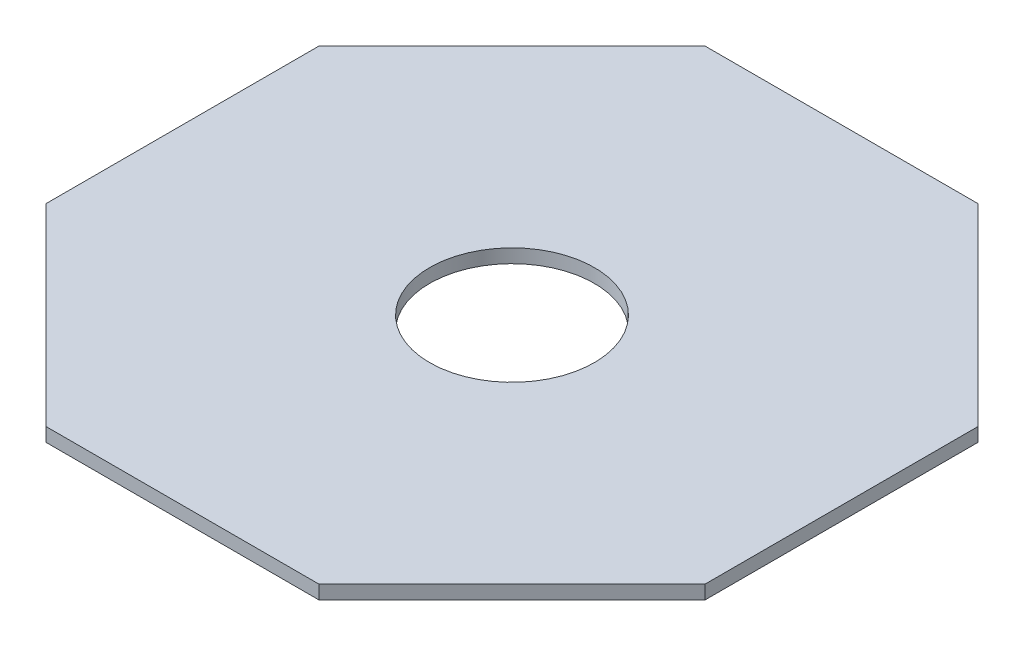
SolidWorks part; units mm, degrees
ref_plane "Front Plane" through (0, 0, 0) normal (0, 0, 1) x (1, 0, 0)
ref_plane "Top Plane" through (0, 0, 0) normal (0, 1, 0) x (1, 0, 0)
ref_plane "Right Plane" through (0, 0, 0) normal (1, 0, 0) x (0, 0, -1)
sketch "Sketch1" plane through (0, 0, 0) normal (0, 1, 0) x (1, 0, 0)
  line L0 (-2.3657, 0) -> (-2.3657, 182.3554) construction
  line L1 (63.1261, 152.4) -> (-63.1261, 152.4)
  line L2 (-63.1261, 152.4) -> (-152.4, 63.1261)
  line L3 (-152.4, 63.1261) -> (-152.4, -63.1261)
  line L4 (-152.4, -63.1261) -> (-63.1261, -152.4)
  line L5 (-63.1261, -152.4) -> (63.1261, -152.4)
  line L6 (63.1261, -152.4) -> (152.4, -63.1261)
  line L7 (152.4, -63.1261) -> (152.4, 63.1261)
  line L8 (152.4, 63.1261) -> (63.1261, 152.4)
  circle A0 centre (0, 0) radius 152.4 construction
  dimension "D1" = 304.8
extrude "Boss-Extrude1" add sketch "Sketch1" along normal blind 6.35
sketch "Sketch2" plane through (0, 6.35, 0) normal (0, 1, 0) x (1, 0, 0)
  circle A0 centre (0, 0) radius 38.1
  dimension "D1" = 76.2
extrude "Cut-Extrude1" cut sketch "Sketch2" against normal through all both and the other way through all
